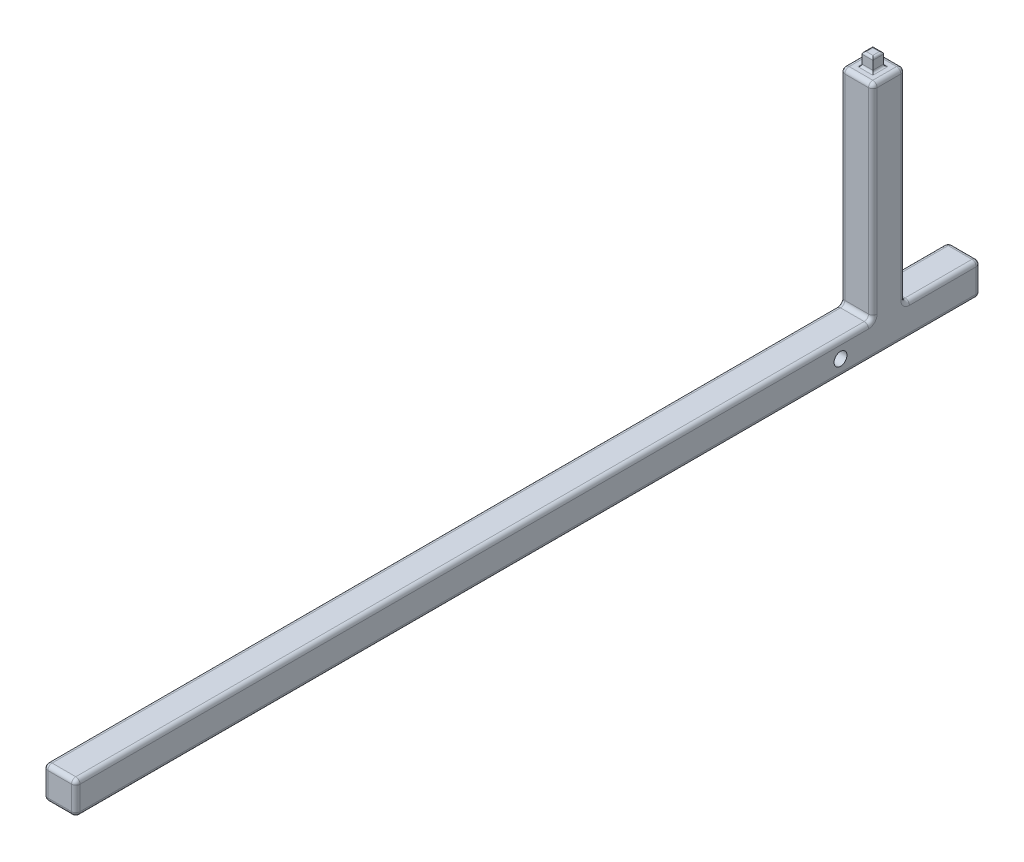
SolidWorks part; units mm, degrees
material "1023 Carbon Steel Sheet (SS)"
ref_plane "Ön Düzlem" through (0, 0, 0) normal (0, 0, 1) x (1, 0, 0)
ref_plane "Üst Düzlem" through (0, 0, 0) normal (0, 1, 0) x (1, 0, 0)
ref_plane "Sağ Düzlem" through (0, 0, 0) normal (1, 0, 0) x (0, 0, -1)
sketch "Sketch1" plane through (0, 0, 0) normal (0, 0, 1) x (1, 0, 0)
  line L0 (-7.5, 108) -> (-7.5, 38)
  line L1 (7.5, 108) -> (7.5, 38)
  line L2 (-7.5, 108) -> (7.5, 108)
  point P4 (0, 108)
  dimension "D1" = 70
  dimension "D2" = 15
  dimension "D3" = 38
ref_plane "Plane1" through (7.5, 0, 0) normal (1, 0, 0) x (0, 0, -1)
ref_plane "Plane2" through (-7.5, 0, 0) normal (1, 0, 0) x (0, 0, -1)
ref_plane "Plane3" through (0, 108, 0) normal (0, 1, 0) x (1, 0, 0)
sketch "Sketch12" plane through (0, 108, 0) normal (0, 1, 0) x (1, 0, 0)
  line L0 (-7.5, 0) -> (7.5, 0) construction
  line L1 (-7.5, 0) -> (7.5, 0)
  line L2 (-7.5, 0) -> (-7.5, 15)
  line L3 (-7.5, 15) -> (7.5, 15)
  line L4 (7.5, 0) -> (7.5, 15)
  line L5 (7.5, -70.4233) -> (7.5, 70.4233) construction
  line L6 (-7.5, -53.8536) -> (-7.5, 53.8536) construction
ref_plane "Plane6" through (0, 0, -50) normal (0, 0, 1) x (1, 0, 0)
sketch "Sketch13" plane through (0, 0, -50) normal (0, 0, 1) x (1, 0, 0)
  line L0 (-7.5, 108) -> (-7.5, 38) construction
  line L1 (7.5, 38) -> (-7.5, 38)
  line L2 (7.5, 38) -> (7.5, 53)
  line L3 (7.5, 53) -> (-7.5, 53)
  line L4 (-7.5, 38) -> (-7.5, 53)
extrude "Boss-Extrude3" add sketch "Sketch13" along normal blind 420
extrude "Boss-Extrude4" add sketch "Sketch12" along normal blind 110 from vertex starting at point (-7.5, 38, 0)
sketch "Sketch14" plane through (0, 148, 0) normal (0, 1, 0) x (1, 0, 0)
  line L0 (-7.5, 15) -> (-7.5, 0) construction
  line L1 (-2.5, 10) -> (2.5, 10)
  line L2 (-2.5, 10) -> (-2.5, 5)
  line L3 (-2.5, 5) -> (2.5, 5)
  line L4 (2.5, 10) -> (2.5, 5)
  point P0 (0, 5)
  point P6 (-7.5, 7.5)
  point P11 (-2.5, 7.5)
  dimension "D1" = 5
extrude "Boss-Extrude5" add sketch "Sketch14" along normal blind 6
fillet "Fillet1" radius 2 22 edges at (7.5, 53, -32.5) (-7.5, 53, -32.5) (-7.5, 100.5, 0) (7.5, 100.5, 0) (7.5, 38, 160) (7.5, 45.5, -50) (0, 38, -50) (-7.5, 45.5, -50) (0, 53, -15) (-7.5, 100.5, -15) (0, 148, -15) (7.5, 100.5, -15) (7.5, 148, -7.5) (-7.5, 148, -7.5) (0, 148, 0) (0, 53, 0) (7.5, 53, 185) (-7.5, 38, 160) (0, 38, 370) (-7.5, 45.5, 370) (0, 53, 370) (-7.5, 53, 185)
fillet "Fillet2" radius 1 8 edges at (-2.5, 148, -7.5) (0, 148, -10) (2.5, 148, -7.5) (0, 148, -5) (0, 154, -10) (-2.5, 154, -7.5) (0, 154, -5) (2.5, 154, -7.5)
fillet "Fillet3" radius 2 3 edges at (6.9142, 38.5858, 369.4142) (6.9142, 52.4142, 369.4142) (7.5, 45.5, 370)
fillet "Fillet4" radius 2 3 edges at (6.9142, 52.4142, -49.4142) (-6.9142, 52.4142, -49.4142) (0, 53, -50)
sketch "Sketch15" plane through (-7.5, 0, 0) normal (-1, 0, 0) x (0, 0, 1)
  line L0 (-50, 40) -> (-50, 51) construction
  line L1 (2, 53) -> (368, 53) construction
  circle A0 centre (15, 45.5) radius 3
  dimension "D1" = 6
  dimension "D2" = 65
  dimension "D3" = 7.5
extrude "Cut-Extrude1" cut sketch "Sketch15" against normal through all
